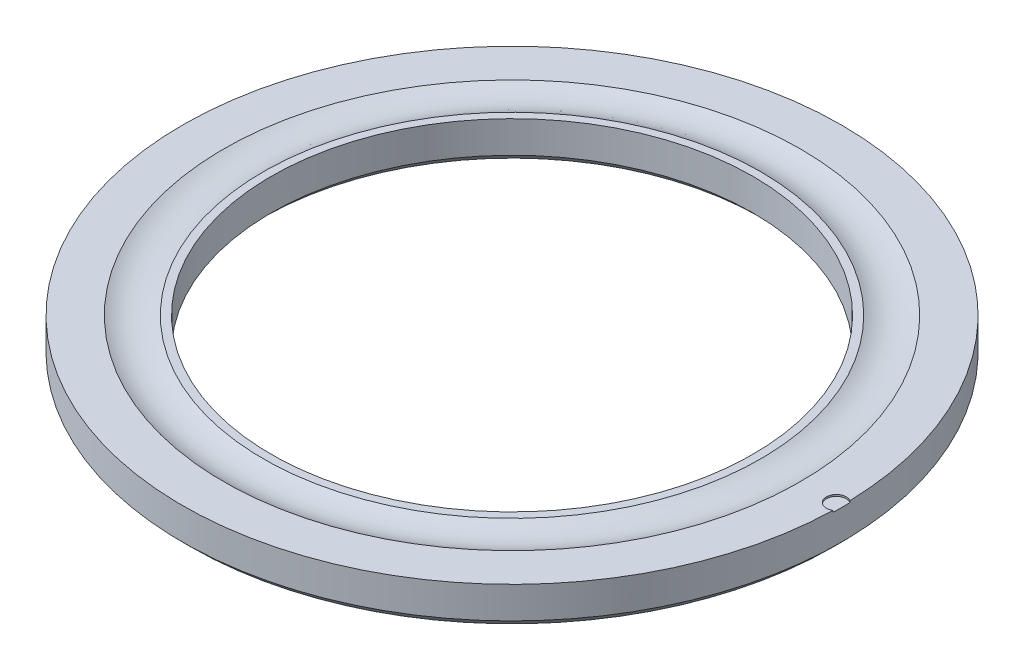
SolidWorks part; units mm, degrees
ref_plane "Front Plane" through (0, 0, 0) normal (0, 0, 1) x (1, 0, 0)
ref_plane "Top Plane" through (0, 0, 0) normal (0, 1, 0) x (1, 0, 0)
ref_plane "Right Plane" through (0, 0, 0) normal (1, 0, 0) x (0, 0, -1)
sketch "Sketch2" plane through (0, 0, 0) normal (0, 0, 1) x (1, 0, 0)
  line L0 (0, 0) -> (0, 15.067) construction
  line L1 (28.5, 0) -> (39, 0)
  line L2 (39, 0) -> (39, 4.75)
  line L3 (39, 4.75) -> (34.1178, 4.75)
  line L4 (28.5, 4.75) -> (28.5, 0)
  line L5 (34.1178, 4.75) -> (29.4317, 4.75) construction
  line L6 (29.4317, 4.75) -> (28.5, 4.75)
  arc A0 (29.4317, 4.75) -> (34.1178, 4.75) centre (31.7748, 9.1735) ccw
  dimension "D1" = 78
  dimension "D2" = 57
  dimension "D3" = 4.75
revolve "Revolve1" add sketch "Sketch2" angle 360 about L0
sketch "Sketch3" plane through (0, 4.75, 0) normal (0, 1, 0) x (1, 0, 0)
  line L0 (0, 0) -> (54.1085, 0) construction
  circle A0 centre (38.3818, 0) radius 1.1747
extrude "Cut-Extrude1" cut sketch "Sketch3" against normal blind 0.2
ref_axis "Axis1" through (38.3818, 4.55, 0) along (0, 1, 0)
chamfer "Chamfer1" distance 1 angle 45 2 edges at (0, 0, -39) (0, 0, -28.5)
